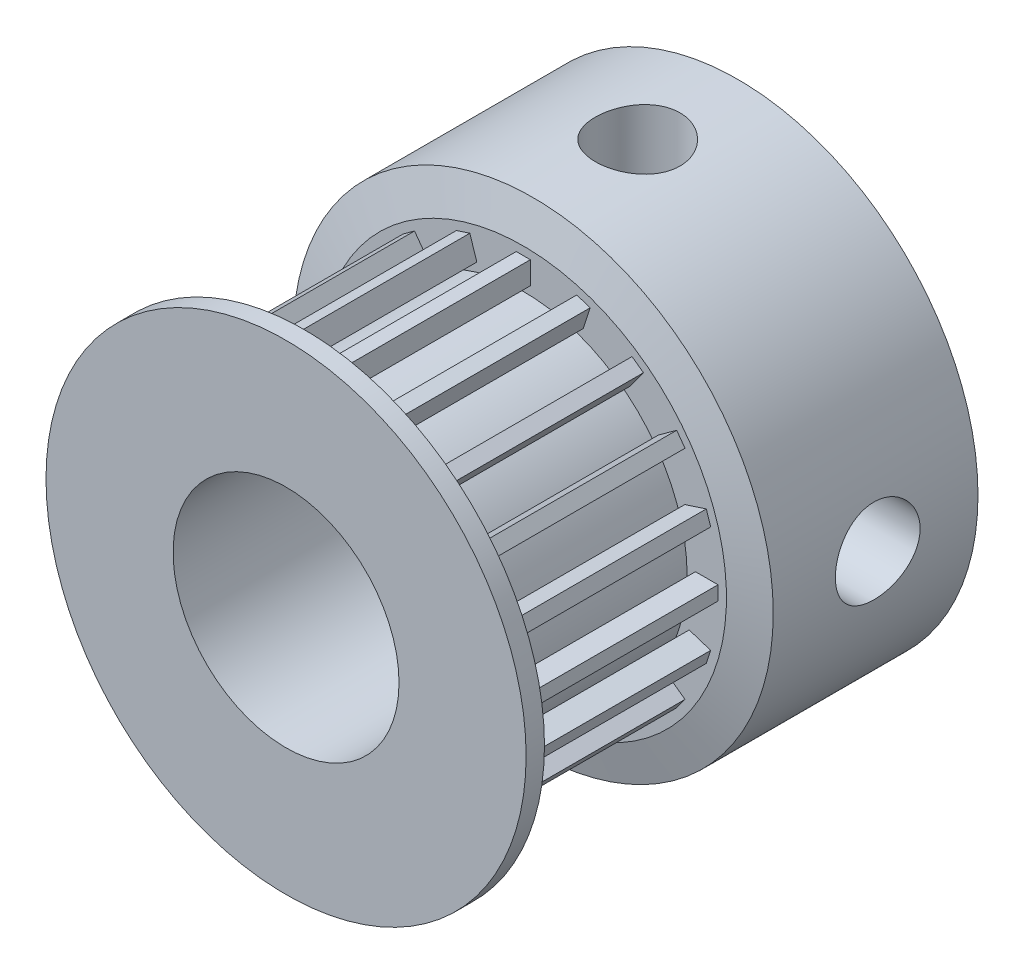
SolidWorks part; units mm, degrees
ref_plane "Front Plane" through (0, 0, 0) normal (0, 0, 1) x (1, 0, 0)
ref_plane "Top Plane" through (0, 0, 0) normal (0, 1, 0) x (1, 0, 0)
ref_plane "Right Plane" through (0, 0, 0) normal (1, 0, 0) x (0, 0, -1)
sketch "Sketch2" plane through (0, 0, 0) normal (1, 0, 0) x (0, 0, -1)
  line L0 (-16, 4) -> (0, 4)
  line L1 (0, 4) -> (0, 8.5)
  line L2 (0, 8.5) -> (-7.6, 8.5)
  line L3 (-7.6, 8.5) -> (-7.6, 5.8)
  line L4 (-7.6, 5.8) -> (-15, 5.8)
  line L5 (-15, 5.8) -> (-15, 8.5)
  line L6 (-15, 8.5) -> (-16, 8.5)
  line L7 (-16, 8.5) -> (-16, 4)
  line L8 (-79.6095, 0) -> (75.5553, 0) construction
  dimension "D1" = 16
  dimension "D2" = 8.5
  dimension "D3" = 1
  dimension "D4" = 7.4
  dimension "D5" = 4
  dimension "D6" = 5.8
revolve "Revolve1" add sketch "Sketch2" angle 360 about L8
chamfer "Chamfer1" distance 0.35 angle 75 1 edges at (8.5, 0, 15) first distance on face at (8.5, 0, 16)
chamfer "Chamfer2" distance 0.35 angle 75 1 edges at (8.5, 0, 7.6) first distance on face at (8.5, 0, 7.6)
sketch "Sketch4" plane through (0, 0, 7.6) normal (0, 0, 1) x (1, 0, 0)
  line L0 (1.6457, 5.8738) -> (1.8929, 6.6347)
  line L1 (1.8929, 6.6347) -> (2.3684, 6.4802)
  line L2 (-0.25, 6.0949) -> (-0.25, 6.8949)
  line L3 (-0.25, 6.8949) -> (0.25, 6.8949)
  line L4 (0.25, 6.0949) -> (0.25, 6.8949)
  line L5 (2.1212, 5.7193) -> (2.3684, 6.4802)
  line L6 (3.3802, 5.0778) -> (3.8505, 5.725)
  line L7 (3.8505, 5.725) -> (4.255, 5.4311)
  line L8 (3.7847, 4.7839) -> (4.255, 5.4311)
  line L9 (4.7839, 3.7847) -> (5.4311, 4.255)
  line L10 (5.4311, 4.255) -> (5.725, 3.8505)
  line L11 (5.0778, 3.3802) -> (5.725, 3.8505)
  line L12 (5.7193, 2.1212) -> (6.4802, 2.3684)
  line L13 (6.4802, 2.3684) -> (6.6347, 1.8929)
  line L14 (5.8738, 1.6457) -> (6.6347, 1.8929)
  line L15 (6.0949, 0.25) -> (6.8949, 0.25)
  line L16 (6.8949, 0.25) -> (6.8949, -0.25)
  line L17 (6.0949, -0.25) -> (6.8949, -0.25)
  line L18 (5.8738, -1.6457) -> (6.6347, -1.8929)
  line L19 (6.6347, -1.8929) -> (6.4802, -2.3684)
  line L20 (5.7193, -2.1212) -> (6.4802, -2.3684)
  line L21 (5.0778, -3.3802) -> (5.725, -3.8505)
  line L22 (5.725, -3.8505) -> (5.4311, -4.255)
  line L23 (4.7839, -3.7847) -> (5.4311, -4.255)
  line L24 (3.7847, -4.7839) -> (4.255, -5.4311)
  line L25 (4.255, -5.4311) -> (3.8505, -5.725)
  line L26 (3.3802, -5.0778) -> (3.8505, -5.725)
  line L27 (2.1212, -5.7193) -> (2.3684, -6.4802)
  line L28 (2.3684, -6.4802) -> (1.8929, -6.6347)
  line L29 (1.6457, -5.8738) -> (1.8929, -6.6347)
  line L30 (0.25, -6.0949) -> (0.25, -6.8949)
  line L31 (0.25, -6.8949) -> (-0.25, -6.8949)
  line L32 (-0.25, -6.0949) -> (-0.25, -6.8949)
  line L33 (-1.6457, -5.8738) -> (-1.8929, -6.6347)
  line L34 (-1.8929, -6.6347) -> (-2.3684, -6.4802)
  line L35 (-2.1212, -5.7193) -> (-2.3684, -6.4802)
  line L36 (-3.3802, -5.0778) -> (-3.8505, -5.725)
  line L37 (-3.8505, -5.725) -> (-4.255, -5.4311)
  line L38 (-3.7847, -4.7839) -> (-4.255, -5.4311)
  line L39 (-4.7839, -3.7847) -> (-5.4311, -4.255)
  line L40 (-5.4311, -4.255) -> (-5.725, -3.8505)
  line L41 (-5.0778, -3.3802) -> (-5.725, -3.8505)
  line L42 (-5.7193, -2.1212) -> (-6.4802, -2.3684)
  line L43 (-6.4802, -2.3684) -> (-6.6347, -1.8929)
  line L44 (-5.8738, -1.6457) -> (-6.6347, -1.8929)
  line L45 (-6.0949, -0.25) -> (-6.8949, -0.25)
  line L46 (-6.8949, -0.25) -> (-6.8949, 0.25)
  line L47 (-6.0949, 0.25) -> (-6.8949, 0.25)
  line L48 (-5.8738, 1.6457) -> (-6.6347, 1.8929)
  line L49 (-6.6347, 1.8929) -> (-6.4802, 2.3684)
  line L50 (-5.7193, 2.1212) -> (-6.4802, 2.3684)
  line L51 (-5.0778, 3.3802) -> (-5.725, 3.8505)
  line L52 (-5.725, 3.8505) -> (-5.4311, 4.255)
  line L53 (-4.7839, 3.7847) -> (-5.4311, 4.255)
  line L54 (-3.7847, 4.7839) -> (-4.255, 5.4311)
  line L55 (-4.255, 5.4311) -> (-3.8505, 5.725)
  line L56 (-3.3802, 5.0778) -> (-3.8505, 5.725)
  line L57 (-2.1212, 5.7193) -> (-2.3684, 6.4802)
  line L58 (-2.3684, 6.4802) -> (-1.8929, 6.6347)
  line L59 (-1.6457, 5.8738) -> (-1.8929, 6.6347)
  arc A0 (-3.3802, 5.0778) -> (-3.7847, 4.7839) centre (0, 0) ccw
  arc A1 (-1.6457, 5.8738) -> (-2.1212, 5.7193) centre (0, 0) ccw
  arc A2 (0.25, 6.0949) -> (-0.25, 6.0949) centre (0, 0) ccw
  arc A3 (2.1212, 5.7193) -> (1.6457, 5.8738) centre (0, 0) ccw
  arc A4 (3.7847, 4.7839) -> (3.3802, 5.0778) centre (0, 0) ccw
  arc A5 (5.0778, 3.3802) -> (4.7839, 3.7847) centre (0, 0) ccw
  arc A6 (5.8738, 1.6457) -> (5.7193, 2.1212) centre (0, 0) ccw
  arc A7 (6.0949, -0.25) -> (6.0949, 0.25) centre (0, 0) ccw
  arc A8 (5.7193, -2.1212) -> (5.8738, -1.6457) centre (0, 0) ccw
  arc A9 (4.7839, -3.7847) -> (5.0778, -3.3802) centre (0, 0) ccw
  arc A10 (3.3802, -5.0778) -> (3.7847, -4.7839) centre (0, 0) ccw
  arc A11 (1.6457, -5.8738) -> (2.1212, -5.7193) centre (0, 0) ccw
  arc A12 (-0.25, -6.0949) -> (0.25, -6.0949) centre (0, 0) ccw
  arc A13 (-2.1212, -5.7193) -> (-1.6457, -5.8738) centre (0, 0) ccw
  arc A14 (-3.7847, -4.7839) -> (-3.3802, -5.0778) centre (0, 0) ccw
  arc A15 (-5.0778, -3.3802) -> (-4.7839, -3.7847) centre (0, 0) ccw
  arc A16 (-5.8738, -1.6457) -> (-5.7193, -2.1212) centre (0, 0) ccw
  arc A17 (-6.0949, 0.25) -> (-6.0949, -0.25) centre (0, 0) ccw
  arc A18 (-5.7193, 2.1212) -> (-5.8738, 1.6457) centre (0, 0) ccw
  arc A19 (-4.7839, 3.7847) -> (-5.0778, 3.3802) centre (0, 0) ccw
  dimension "D1" = 12.2
  dimension "D2" = 0.5
  dimension "D3" = 0.25
  dimension "D4" = 0.8
  dimension "D5" = 20
extrude "Boss-Extrude1" add sketch "Sketch4" along normal up to surface (7.4 mm away) up to face at (7.1938, 0, 15)
ref_plane "Plane1" through (0, 8.9, 0) normal (0, 1, 0) x (-1, 0, 0)
sketch "Sketch6" plane through (0, 8.9, 0) normal (0, 1, 0) x (-1, 0, 0)
  line L2 (0, 3.55) -> (4.2063, 3.55) construction
  circle A0 centre (0, 3.55) radius 1.5
  dimension "D1" = 3
  dimension "D2" = 3.55
extrude "Cut-Extrude1" cut sketch "Sketch6" against normal blind 10
pattern_circular "CirPattern1" count 2 every 270 about axis through (0, 0, 0) along (0, 0, 1) of "Cut-Extrude1"
